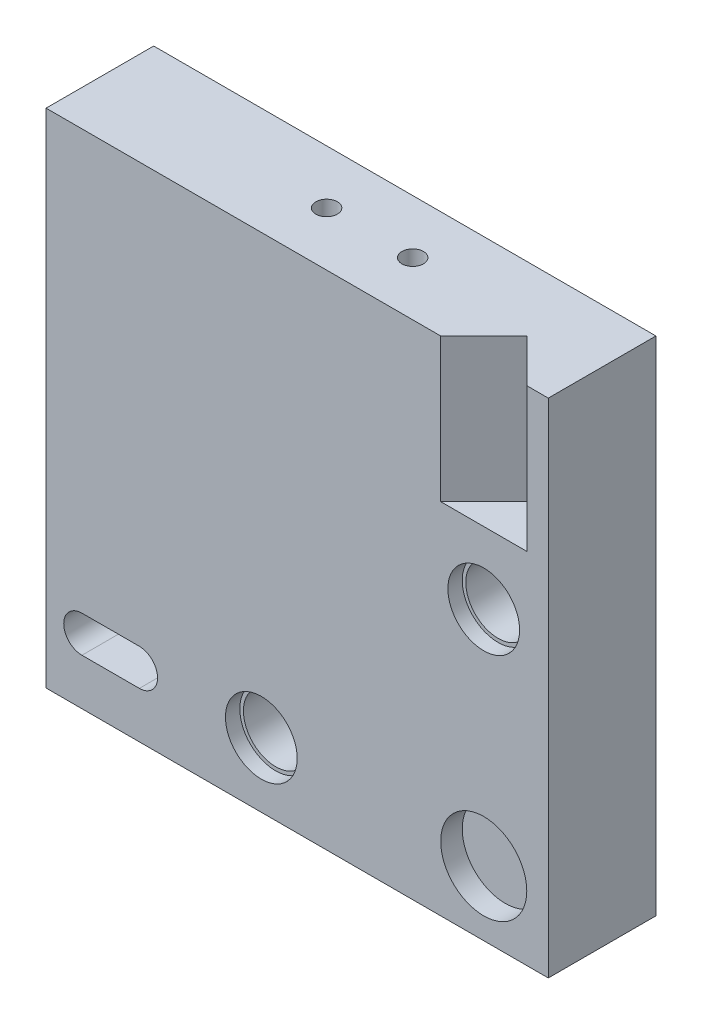
SolidWorks part; units mm, degrees
ref_plane "Front Plane" through (0, 0, 0) normal (0, 0, 1) x (1, 0, 0)
ref_plane "Top Plane" through (0, 0, 0) normal (0, 1, 0) x (1, 0, 0)
ref_plane "Right Plane" through (0, 0, 0) normal (1, 0, 0) x (0, 0, -1)
sketch "Sketch1" plane through (0, 0, 0) normal (0, 0, 1) x (1, 0, 0)
  line L1 (-17.7337, 13.9901) -> (17.2663, 13.9901)
  line L2 (-17.7337, 13.9901) -> (-17.7337, -21.0099)
  line L3 (-17.7337, -21.0099) -> (17.2663, -21.0099)
  line L4 (17.2663, 13.9901) -> (17.2663, -21.0099)
  dimension "D1" = 35
  dimension "D2" = 35
extrude "Boss-Extrude1" add sketch "Sketch1" along normal blind 7.5
sketch "Sketch2" plane through (0, 0, 0) normal (0, 0, -1) x (-1, 0, 0)
  line L0 (17.7337, 2.9901) -> (-6.2663, 2.9901)
  line L1 (17.7337, 13.9901) -> (17.7337, -21.0099) construction
  line L2 (-6.2663, 2.9901) -> (-6.2663, -10.0099)
  line L3 (-6.2663, -10.0099) -> (17.7337, -10.0099)
  line L4 (-17.2663, 13.9901) -> (17.7337, 13.9901) construction
  line L6 (-17.2663, -21.0099) -> (-17.2663, 13.9901) construction
  line L7 (17.7337, 2.9901) -> (17.7337, -10.0099)
  dimension "D1" = 13
  dimension "D2" = 11
  dimension "D3" = 11
extrude "Cut-Extrude2" cut sketch "Sketch2" against normal blind 5
sketch "Sketch4" plane through (0, 0, 7.5) normal (0, 0, 1) x (1, 0, 0)
  line L0 (-17.7337, 13.9901) -> (-17.7337, -21.0099) construction
  line L1 (-17.7337, -21.0099) -> (17.2663, -21.0099) construction
  line L3 (-11.2337, -15.2399) -> (-15.2337, -15.2399)
  line L5 (-11.2337, -17.7799) -> (-15.2337, -17.7799)
  line L7 (-11.2337, -15.2399) -> (-15.2337, -17.7799) construction
  line L8 (-11.2337, -17.7799) -> (-15.2337, -15.2399) construction
  arc A0 (-15.2337, -15.2399) -> (-15.2337, -17.7799) centre (-15.2337, -16.5099) ccw
  arc A1 (-11.2337, -15.2399) -> (-11.2337, -17.7799) centre (-11.2337, -16.5099) cw
  point P0 (-13.2337, -16.5099)
  dimension "D3" = 4
  dimension "D1" = 4.5
  dimension "D2" = 4.5
  dimension "D4" = 2.54
sketch "Sketch5" plane through (0, 0, 7.5) normal (0, 0, 1) x (1, 0, 0)
  line L0 (-17.7337, -21.0099) -> (17.2663, -21.0099) construction
  line L1 (17.2663, -21.0099) -> (17.2663, 13.9901) construction
  circle A0 centre (12.7663, -1.0099) radius 2.5
  circle A1 centre (-2.7337, -16.5099) radius 2.5
  dimension "D5" = 5
  dimension "D6" = 5
  dimension "D1" = 20
  dimension "D2" = 20
  dimension "D3" = 4.5
  dimension "D4" = 4.5
sketch "Sketch10" plane through (0, 13.9901, 0) normal (0, 1, 0) x (1, 0, 0)
  line L0 (17.2663, -7.5) -> (17.2663, 0) construction
  line L1 (17.2663, 0) -> (-17.7337, 0) construction
  line L2 (17.2663, -7.5) -> (-17.7337, -7.5) construction
  circle A0 centre (4.0663, -3.75) radius 0.75
  circle A1 centre (-1.9337, -3.75) radius 0.75
  dimension "D1" = 13.2
  dimension "D2" = 1.5
  dimension "D3" = 1.5
  dimension "D4" = 3.75
  dimension "D5" = 3.75
  dimension "D6" = 6
extrude "Cut-Extrude7" cut sketch "Sketch10" against normal blind 7
extrude "Cut-Extrude11" cut sketch "Sketch5" against normal blind 1
sketch "Sketch11" plane through (0, 0, 6.5) normal (0, 0, 1) x (1, 0, 0)
  circle A0 centre (-2.7337, -16.5099) radius 2.25
  circle A1 centre (12.7663, -1.0099) radius 2.25
  dimension "D1" = 4.5
  dimension "D2" = 4.5
extrude "Cut-Extrude12" cut sketch "Sketch11" against normal blind 5
sketch "Sketch13" plane through (0, -21.0099, 0) normal (0, -1, 0) x (1, 0, 0)
  line L0 (9.7663, 7.5) -> (12.7663, 4.5)
  line L1 (-17.7337, 7.5) -> (17.2663, 7.5) construction
  line L2 (12.7663, 4.5) -> (15.7663, 7.5)
  line L3 (17.2663, 7.5) -> (17.2663, 0) construction
  line L4 (9.7663, 7.5) -> (15.7663, 7.5)
  dimension "D1" = 3
  dimension "D2" = 135
  dimension "D3" = 4.5
extrude "Cut-Extrude13" cut sketch "Sketch13" against normal blind 10
sketch "Sketch15" plane through (0, 13.9901, 0) normal (0, 1, 0) x (1, 0, 0)
  line L0 (9.7663, -7.5) -> (12.7663, -4.5)
  line L1 (17.2663, -7.5) -> (-17.7337, -7.5) construction
  line L2 (12.7663, -4.5) -> (15.7663, -7.5)
  line L3 (9.7663, -7.5) -> (15.7663, -7.5)
  dimension "D1" = 0
  dimension "D2" = 0
  dimension "D3" = 0
extrude "Cut-Extrude14" cut sketch "Sketch15" against normal blind 10
extrude "Cut-Extrude15" cut sketch "Sketch4" against normal blind 4
sketch "Sketch16" plane through (0, -11.0099, 0) normal (0, -1, 0) x (-1, 0, 0)
  line L0 (-9.7663, -7.5) -> (-15.7663, -7.5)
  line L1 (-15.7663, -7.5) -> (-9.7663, -7.5) construction
  line L2 (-15.7663, -7.5) -> (-12.7663, -4.5)
  line L3 (-12.7663, -4.5) -> (-15.7663, -7.5) construction
  line L4 (-12.7663, -4.5) -> (-9.7663, -7.5)
extrude "Boss-Extrude2" add sketch "Sketch16" along normal blind 10
sketch "Sketch17" plane through (0, 0, 7.5) normal (0, 0, 1) x (1, 0, 0)
  line L0 (-17.7337, -21.0099) -> (17.2663, -21.0099) construction
  line L1 (17.2663, -21.0099) -> (17.2663, 13.9901) construction
  circle A0 centre (12.7663, -16.5099) radius 3
  dimension "D1" = 6
  dimension "D2" = 4.5
  dimension "D3" = 4.5
extrude "Cut-Extrude16" cut sketch "Sketch17" against normal blind 1.5
